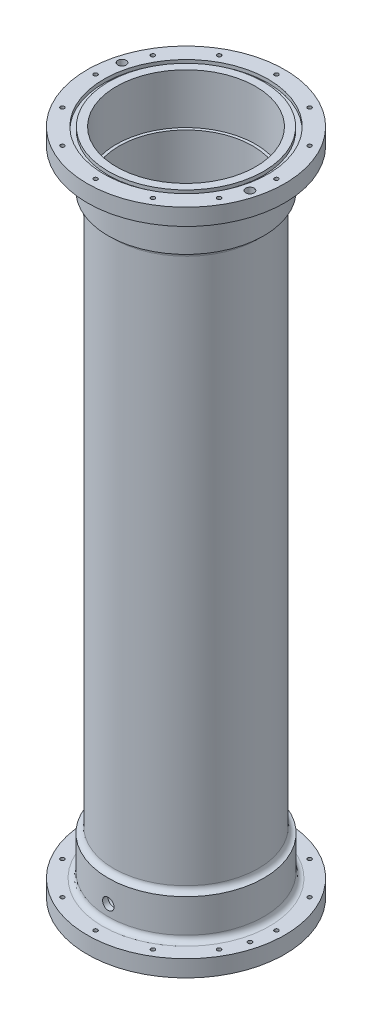
SolidWorks part; units mm, degrees
material "7075-T6 (SN)"
ref_plane "Front Plane" through (0, 0, 0) normal (0, 0, 1) x (1, 0, 0)
ref_plane "Top Plane" through (0, 0, 0) normal (0, 1, 0) x (1, 0, 0)
ref_plane "Right Plane" through (0, 0, 0) normal (1, 0, 0) x (0, 0, -1)
sketch "Sketch2" plane through (0, 0, 0) normal (0, 1, 0) x (1, 0, 0)
  circle A0 centre (0, 0) radius 38.1
  circle A1 centre (0, 0) radius 41.275
  dimension "D1" = 82.55
  dimension "D2" = 76.2
extrude "Base Cylinder" add sketch "Sketch2" along normal blind 381
sketch "Sketch3" plane through (0, 0, 0) normal (0, -1, 0) x (1, 0, 0)
  circle A0 centre (0, 0) radius 38.1
  circle A1 centre (0, 0) radius 56.3562
  dimension "D1" = 112.7125
extrude "Aft Flange" add sketch "Sketch3" against normal blind 9.525
sketch "Sketch34" plane through (0, 0, 0) normal (0, -1, 0) x (1, 0, 0)
  circle A0 centre (0, 0) radius 39.75
  dimension "D1" = 79.5
extrude "TemperatureInsert" cut sketch "Sketch34" against normal blind 28.575
sketch "Sketch6" plane through (0, 0, 0) normal (0, -1, 0) x (1, 0, 0)
  circle A0 centre (0, 0) radius 46.9011
  circle A1 centre (0, 0) radius 44.2849
  dimension "D1" = 93.8022
  dimension "D2" = 88.5698
extrude "Aft O-Ring" cut sketch "Sketch6" against normal blind 1.9812
sketch "Sketch33" plane through (0, 9.525, 0) normal (0, 1, 0) x (1, 0, 0)
  circle A0 centre (0, 0) radius 41.275
  circle A1 centre (0, 0) radius 44.45
  dimension "D1" = 82.55
  dimension "D2" = 88.9
extrude "CriticalBoss" add sketch "Sketch33" along normal blind 22.225
fillet "Fillet1" radius 3.175 2 edges at (0, 9.525, -44.45) (0, 31.75, 41.275)
sketch "Sketch For Bolt Holes" plane through (0, 0, 0) normal (0, -1, 0) x (1, 0, 0)
  circle A0 centre (-51.6255, 0) radius 1.5875
  circle A1 centre (-44.709, 25.8128) radius 1.5875
  circle A2 centre (-25.8128, 44.709) radius 1.5875
  circle A3 centre (0, 51.6255) radius 1.5875
  circle A4 centre (25.8127, 44.709) radius 1.5875
  circle A5 centre (44.709, 25.8128) radius 1.5875
  circle A6 centre (51.6255, 0) radius 1.5875
  circle A7 centre (44.709, -25.8127) radius 1.5875
  circle A8 centre (25.8128, -44.709) radius 1.5875
  circle A9 centre (0, -51.6255) radius 1.5875
  circle A10 centre (-25.8127, -44.709) radius 1.5875
  circle A11 centre (-44.709, -25.8128) radius 1.5875
  point P36 (0, 0)
  dimension "D2" = 3.175
  dimension "D1" = 51.6255
  dimension "D3" = 12
hole_wizard "Bolt Circle" positions "Sketch8" profile "Sketch9" hole size "#4-40" standard "ANSI Inch" end condition up to next
sketch "Sketch8" plane through (0, 0, 0) normal (0, -1, 0) x (-1, 0, 0)
  point P0 (-25.8127, -44.709)
  point P3 (-44.709, -25.8128)
  point P6 (-51.6255, 0)
  point P9 (-44.709, 25.8127)
  point P12 (-25.8128, 44.709)
  point P15 (0, 51.6255)
  point P18 (25.8127, 44.709)
  point P21 (44.709, 25.8128)
  point P24 (51.6255, 0)
  point P27 (44.709, -25.8128)
  point P30 (25.8128, -44.709)
  point P33 (0, -51.6255)
  point P36 (-25.8127, -44.709)
  point P38 (-44.709, -25.8128)
  point P40 (-51.6255, 0)
sketch "Sketch9" plane through (25.8127, 0, 44.709) normal (1, 0, 0) x (0, 0, -1)
  line L0 (0, 0) -> (0, 381)
  line L1 (0, 381) -> (1.1303, 381)
  line L2 (1.1303, 381) -> (1.1303, 0)
  line L5 (1.1303, 0) -> (0, 0)
  line L11 (0, -6.35) -> (0, 107.95) construction
  dimension "Thru Hole Dia." = 2.2606
  dimension "Thru Hole Depth" = 381
sketch "Dowel Hole Sketch" plane through (0, 0, 0) normal (0, -1, 0) x (1, 0, 0)
  line L0 (0, 0) -> (-51.6255, 0) construction
  line L1 (0, 0) -> (-49.8664, -13.3617) construction
  line L2 (0, 0) -> (0, -51.6255) construction
  line L3 (0, 0) -> (49.8664, 13.3617) construction
  circle A0 centre (0, 0) radius 51.6255
  circle A1 centre (-49.8664, -13.3617) radius 4.6172
  circle A2 centre (49.8664, 13.3617) radius 3.4532
  dimension "D1" = 15
hole_wizard "Hole1" positions "Sketch14" profile "Sketch12" legacy end condition up to next
sketch "Sketch14" plane through (0, 0, 0) normal (0, -1, 0) x (-1, 0, 0)
  point P0 (49.8664, 13.3617)
  point P3 (-49.8664, -13.3617)
sketch "Sketch12" plane through (-49.8664, 0, -13.3617) normal (1, 0, 0) x (0, 0, -1)
  line L0 (0, 0) -> (0, 381)
  line L1 (0, 381) -> (1.1906, 381)
  line L2 (1.1906, 381) -> (1.1906, 4.7625)
  line L3 (1.1906, 4.7625) -> (2.3813, 4.7625)
  line L4 (2.3813, 4.7625) -> (2.3813, 0)
  line L5 (2.3813, 0) -> (0, 0)
  line L6 (0, 110) -> (0, -10) construction
  dimension "Diameter" = 2.3813
  dimension "Depth" = 381
  dimension "C-Bore Diameter" = 4.7625
  dimension "C-Bore Depth" = 4.7625
ref_plane "Hoop Mid-Plane" through (0, 190.5, 0) normal (0, 1, 0) x (1, 0, 0)
ref_plane "PressureTapHolePlane" through (0, 0, 44.45) normal (0, 0, 1) x (1, 0, 0)
ref_plane "TemperatureTapPlane" through (0, 0, -44.45) normal (0, 0, 1) x (1, 0, 0)
sketch "ThermoHole" plane through (0, 0, -44.45) normal (0, 0, 1) x (1, 0, 0)
  line L0 (-56.3562, 0) -> (56.3562, 0) construction
  circle A0 centre (0, 19.05) radius 3.175
  dimension "D1" = 19.05
  dimension "D2" = 6.35
hole_wizard "1/8 NPT Tapped ThermocoupleHole" positions "Sketch43" profile "Sketch44" size "1/8" standard "ANSI Inch"
sketch "Sketch43" plane through (0, 0, -44.45) normal (0, 0, 1) x (1, 0, 0)
  line L0 (-56.3562, 0) -> (56.3562, 0) construction
  point P0 (0, 19.05)
  dimension "D1" = 19.05
sketch "Sketch44" plane through (0, 19.05, -44.45) normal (1, 0, 0) x (0, 1, 0)
  line L0 (0, 0) -> (0, 14.2175)
  line L1 (4.2164, 11.684) -> (0, 14.2175)
  line L2 (-4.2164, 11.684) -> (0, 14.2175) construction
  line L3 (4.2164, 11.684) -> (4.2164, 6.858)
  line L4 (4.2164, 6.858) -> (4.9362, 6.858)
  line L5 (4.9362, 6.858) -> (5.1415, 0)
  line L6 (-4.9362, 6.858) -> (-5.1415, 0) construction
  line L7 (5.1415, 0) -> (0, 0)
  line L8 (0, -6.35) -> (0, 107.95) construction
  line L11 (-4.2164, 6.858) -> (-4.9362, 6.858) construction
  dimension "Tap Drill Dia." = 8.4328
  dimension "Tap Drill Depth" = 11.684
  dimension "Thread Dia." = 10.283
  dimension "Thread Angle" = 3.43
  dimension "Thread Depth" = 6.858
  dimension "Drill Angle" = 118
mirror "Mirror1" about plane through (0, 190.5, 0) normal (0, 1, 0) of "Hole1", "Bolt Circle", "Fillet1", "CriticalBoss", "Aft O-Ring", "TemperatureInsert", "Aft Flange"
hole_wizard "5/16-18 Tapped Hole1" positions "Sketch48" profile "Sketch49" tap size "5/16-18" standard "ANSI Inch"
sketch "Sketch48" plane through (0, 0, 44.45) normal (0, 0, 1) x (1, 0, 0)
  line L0 (-56.3562, 0) -> (56.3562, 0) construction
  point P0 (0, 19.05)
  dimension "D1" = 19.05
sketch "Sketch49" plane through (0, 19.05, 44.45) normal (1, 0, 0) x (0, -1, 0)
  line L0 (0, 0) -> (0, 5.1361)
  line L1 (0, 5.1361) -> (3.2639, 3.175)
  line L2 (3.2639, 3.175) -> (3.2639, 0)
  line L5 (3.2639, 0) -> (0, 0)
  line L10 (0, 5.1361) -> (-3.2639, 3.175) construction
  line L11 (0, -6.35) -> (0, 107.95) construction
  dimension "Tap Drill Dia." = 6.5278
  dimension "Tap Drill Depth" = 3.175
  dimension "Drill Angle" = 118
cosmetic thread "Hole Thread1" parameters "D1"=3.175, "D2"=7.9375
sketch "Sketch50" plane through (0, 0, 44.45) normal (0, 0, 1) x (1, 0, 0)
  circle A0 centre (0, 19.05) radius 0.7937
  dimension "D1" = 1.5875
extrude "Cut-Extrude1" cut sketch "Sketch50" against normal up to next
